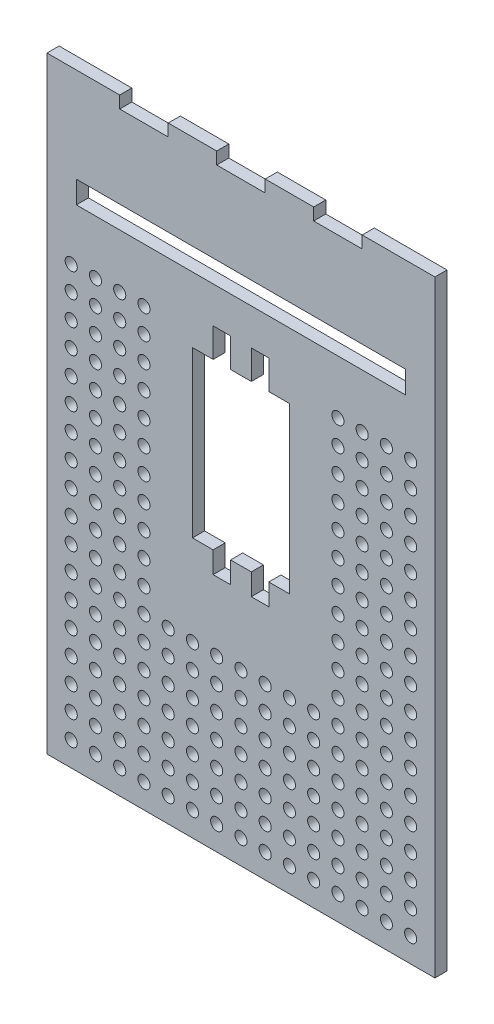
SolidWorks part; units mm, degrees
ref_plane "Front Plane" through (0, 0, 0) normal (0, 0, 1) x (1, 0, 0)
ref_plane "Top Plane" through (0, 0, 0) normal (0, 1, 0) x (1, 0, 0)
ref_plane "Right Plane" through (0, 0, 0) normal (1, 0, 0) x (0, 0, -1)
sketch "Sketch1" plane through (0, 0, 0) normal (0, 0, 1) x (1, 0, 0)
  line L1 (50.8, -79.502) -> (-50.8, -79.502)
  line L2 (50.8, -79.502) -> (50.8, 79.502)
  line L3 (50.8, 79.502) -> (-50.8, 79.502)
  line L4 (-50.8, -79.502) -> (-50.8, 79.502)
  line L5 (50.8, -79.502) -> (-50.8, 79.502) construction
  line L6 (50.8, 79.502) -> (-50.8, -79.502) construction
  point P0 (0, 0)
  dimension "D1" = 101.6
  dimension "D2" = 79.502
extrude "Boss-Extrude1" add sketch "Sketch1" along normal blind 3.175
ref_axis "Axis1" through (0, 0, 0) along (0, 0, 1)
sketch "Sketch3" plane through (0, 0, 3.175) normal (0, 0, 1) x (1, 0, 0)
  line L1 (-12.7, 31.75) -> (12.7, 31.75)
  line L2 (-12.7, 31.75) -> (-12.7, -11.43)
  line L3 (-12.7, -11.43) -> (12.7, -11.43)
  line L4 (12.7, 31.75) -> (12.7, -11.43)
  point P4 (0, 31.75)
  dimension "D1" = 25.4
  dimension "D2" = 11.43
  dimension "D3" = 31.75
extrude "Cut-Extrude1" cut sketch "Sketch3" against normal up to next
sketch "Sketch4" plane through (0, 0, 3.175) normal (0, 0, 1) x (1, 0, 0)
  line L1 (-6.35, 76.327) -> (6.35, 76.327)
  line L2 (-6.35, 76.327) -> (-6.35, 79.502)
  line L3 (-6.35, 79.502) -> (6.35, 79.502)
  line L4 (6.35, 76.327) -> (6.35, 79.502)
  line L5 (19.05, 79.502) -> (31.75, 79.502)
  line L6 (19.05, 76.327) -> (19.05, 79.502)
  line L7 (19.05, 76.327) -> (31.75, 76.327)
  line L8 (31.75, 76.327) -> (31.75, 79.502)
  line L17 (0, -1.7463) -> (0, 1.7463) construction
  line L18 (-31.75, 76.327) -> (-31.75, 79.502)
  line L19 (-19.05, 76.327) -> (-31.75, 76.327)
  line L20 (-19.05, 76.327) -> (-19.05, 79.502)
  line L21 (-19.05, 79.502) -> (-31.75, 79.502)
  line L22 (50.8, 79.502) -> (-50.8, 79.502) construction
  point P6 (0, 79.502)
  dimension "D1" = 3.175
  dimension "D2" = 12.7
  dimension "D3" = 2
  dimension "D4" = 1
extrude "Cut-Extrude2" cut sketch "Sketch4" against normal up to next
sketch "Sketch5" plane through (0, 0, 3.175) normal (0, 0, 1) x (1, 0, 0)
  line L1 (-7.286, 39.37) -> (-2.714, 39.37)
  line L2 (-7.286, 39.37) -> (-7.286, 31.75)
  line L3 (-7.286, 31.75) -> (-2.714, 31.75)
  line L4 (-2.714, 39.37) -> (-2.714, 31.75)
  line L5 (12.7, 31.75) -> (-12.7, 31.75) construction
  line L6 (0, -1.7463) -> (0, 1.7463) construction
  line L7 (2.714, 39.37) -> (2.714, 31.75)
  line L8 (7.286, 31.75) -> (2.714, 31.75)
  line L9 (7.286, 39.37) -> (7.286, 31.75)
  line L10 (7.286, 39.37) -> (2.714, 39.37)
  line L11 (-12.7, -11.43) -> (12.7, -11.43) construction
  line L12 (-7.286, -11.43) -> (-2.714, -11.43)
  line L13 (-7.286, -11.43) -> (-7.286, -17.0574)
  line L14 (-7.286, -17.0574) -> (-2.714, -17.0574)
  line L15 (-2.714, -11.43) -> (-2.714, -17.0574)
  line L16 (0, -52.7486) -> (0, 52.7486) construction
  line L17 (2.714, -11.43) -> (2.714, -17.0574)
  line L18 (7.286, -17.0574) -> (2.714, -17.0574)
  line L19 (7.286, -11.43) -> (7.286, -17.0574)
  line L20 (7.286, -11.43) -> (2.714, -11.43)
  arc A0 (-17.0133, 2.9779) -> (17.0133, 2.9779) centre (0, 0) ccw construction
  point P5 (-5, 39.37)
  dimension "D1" = 4.572
  dimension "D2" = 7.62
extrude "Cut-Extrude3" cut sketch "Sketch5" against normal up to next
sketch "Sketch6" plane through (0, 0, 3.175) normal (0, 0, 1) x (1, 0, 0)
  line L5 (-31.75, 79.502) -> (-50.8, 79.502) construction
  line L6 (-43.1171, 54.737) -> (43.1171, 54.737)
  line L7 (-43.1171, 54.737) -> (-43.1171, 48.895)
  line L8 (-43.1171, 48.895) -> (43.1171, 48.895)
  line L9 (43.1171, 54.737) -> (43.1171, 48.895)
  point P0 (0, 54.737)
  point P13 (-43.1171, 51.816)
  dimension "D1" = 5.842
  dimension "D2" = 86.2342
  dimension "D3" = 27.686
extrude "Cut-Extrude4" cut sketch "Sketch6" against normal up to next
sketch "Sketch7" plane through (0, 0, 3.175) normal (0, 0, 1) x (1, 0, 0)
  line L0 (-50.8, -1.27) -> (50.8, -1.27) construction
  line L1 (-50.8, 79.502) -> (-50.8, -79.502) construction
  line L2 (50.8, -79.502) -> (50.8, 79.502) construction
  line L3 (-31.75, 79.502) -> (-50.8, 79.502) construction
  dimension "D1" = 80.772
ref_plane "Plane1" through (0, -1.27, 0) normal (0, -1, 0) x (1, 0, 0)
sketch "Sketch8" plane through (0, 0, 3.175) normal (0, 0, 1) x (1, 0, 0)
  line L0 (-20.32, 28.2222) -> (20.32, 28.2222) construction
  line L1 (86.378, -28.9767) -> (84.2952, -28.9767)
  line L2 (86.378, -28.9767) -> (86.378, 28.2222)
  line L3 (86.378, 28.2222) -> (84.2952, 28.2222)
  line L4 (84.2952, -28.9767) -> (84.2952, 28.2222)
  line L5 (86.378, -28.9767) -> (84.2952, 28.2222) construction
  line L6 (86.378, 28.2222) -> (84.2952, -28.9767) construction
  line L7 (88.156, -6.5532) -> (88.156, 23.5712) construction
  line L8 (0, -1.7463) -> (0, 1.7463) construction
  line L9 (-86.378, 28.2222) -> (-84.2952, -28.9767) construction
  line L10 (-86.378, -28.9767) -> (-84.2952, 28.2222) construction
  line L11 (-84.2952, -28.9767) -> (-84.2952, 28.2222)
  line L12 (-86.378, 28.2222) -> (-84.2952, 28.2222)
  line L13 (-86.378, -28.9767) -> (-86.378, 28.2222)
  line L14 (-86.378, -28.9767) -> (-84.2952, -28.9767)
  point P0 (85.3366, -0.3772)
  point P8 (85.3366, 28.2222)
  point P17 (-85.3366, 28.2222)
  point P18 (-85.3366, -0.3772)
  dimension "D1" = 2.0828
  dimension "D2" = 57.1989
  dimension "D3" = 1.778
extrude "Cut-Extrude5" cut sketch "Sketch8" against normal up to next rebuild error yes
sketch "Sketch9" plane through (0, 0, 3.175) normal (0, 0, 1) x (1, 0, 0)
  line L0 (-50.8, -79.502) -> (50.8, -79.502) construction
  line L1 (-50.8, 79.502) -> (-50.8, -79.502) construction
  circle A0 centre (-44.45, -73.152) radius 1.5875
  circle A1 centre (-38.1, -73.152) radius 1.5875
  circle A2 centre (-31.75, -73.152) radius 1.5875
  circle A3 centre (-25.4, -73.152) radius 1.5875
  circle A4 centre (-19.05, -73.152) radius 1.5875
  circle A5 centre (-12.7, -73.152) radius 1.5875
  circle A6 centre (-6.35, -73.152) radius 1.5875
  circle A7 centre (0, -73.152) radius 1.5875
  circle A8 centre (6.35, -73.152) radius 1.5875
  circle A9 centre (12.7, -73.152) radius 1.5875
  circle A10 centre (19.05, -73.152) radius 1.5875
  circle A11 centre (25.4, -73.152) radius 1.5875
  circle A12 centre (31.75, -73.152) radius 1.5875
  circle A13 centre (38.1, -73.152) radius 1.5875
  circle A14 centre (44.45, -73.152) radius 1.5875
  circle A15 centre (-38.1, -66.802) radius 1.5875
  circle A16 centre (-31.75, -66.802) radius 1.5875
  circle A17 centre (-25.4, -66.802) radius 1.5875
  circle A18 centre (-19.05, -66.802) radius 1.5875
  circle A19 centre (-12.7, -66.802) radius 1.5875
  circle A20 centre (-6.35, -66.802) radius 1.5875
  circle A21 centre (0, -66.802) radius 1.5875
  circle A22 centre (6.35, -66.802) radius 1.5875
  circle A23 centre (12.7, -66.802) radius 1.5875
  circle A24 centre (19.05, -66.802) radius 1.5875
  circle A25 centre (25.4, -66.802) radius 1.5875
  circle A26 centre (31.75, -66.802) radius 1.5875
  circle A27 centre (38.1, -66.802) radius 1.5875
  circle A28 centre (44.45, -66.802) radius 1.5875
  circle A29 centre (-38.1, -60.452) radius 1.5875
  circle A30 centre (-31.75, -60.452) radius 1.5875
  circle A31 centre (-25.4, -60.452) radius 1.5875
  circle A32 centre (-19.05, -60.452) radius 1.5875
  circle A33 centre (-12.7, -60.452) radius 1.5875
  circle A34 centre (-6.35, -60.452) radius 1.5875
  circle A35 centre (0, -60.452) radius 1.5875
  circle A36 centre (6.35, -60.452) radius 1.5875
  circle A37 centre (12.7, -60.452) radius 1.5875
  circle A38 centre (19.05, -60.452) radius 1.5875
  circle A39 centre (25.4, -60.452) radius 1.5875
  circle A40 centre (31.75, -60.452) radius 1.5875
  circle A41 centre (38.1, -60.452) radius 1.5875
  circle A42 centre (44.45, -60.452) radius 1.5875
  circle A43 centre (-38.1, -54.102) radius 1.5875
  circle A44 centre (-31.75, -54.102) radius 1.5875
  circle A45 centre (-25.4, -54.102) radius 1.5875
  circle A46 centre (-19.05, -54.102) radius 1.5875
  circle A47 centre (-12.7, -54.102) radius 1.5875
  circle A48 centre (-6.35, -54.102) radius 1.5875
  circle A49 centre (0, -54.102) radius 1.5875
  circle A50 centre (6.35, -54.102) radius 1.5875
  circle A51 centre (12.7, -54.102) radius 1.5875
  circle A52 centre (19.05, -54.102) radius 1.5875
  circle A53 centre (25.4, -54.102) radius 1.5875
  circle A54 centre (31.75, -54.102) radius 1.5875
  circle A55 centre (38.1, -54.102) radius 1.5875
  circle A56 centre (44.45, -54.102) radius 1.5875
  circle A57 centre (-38.1, -47.752) radius 1.5875
  circle A58 centre (-31.75, -47.752) radius 1.5875
  circle A59 centre (-25.4, -47.752) radius 1.5875
  circle A60 centre (-19.05, -47.752) radius 1.5875
  circle A61 centre (-12.7, -47.752) radius 1.5875
  circle A62 centre (-6.35, -47.752) radius 1.5875
  circle A63 centre (0, -47.752) radius 1.5875
  circle A64 centre (6.35, -47.752) radius 1.5875
  circle A65 centre (12.7, -47.752) radius 1.5875
  circle A66 centre (19.05, -47.752) radius 1.5875
  circle A67 centre (25.4, -47.752) radius 1.5875
  circle A68 centre (31.75, -47.752) radius 1.5875
  circle A69 centre (38.1, -47.752) radius 1.5875
  circle A70 centre (44.45, -47.752) radius 1.5875
  circle A71 centre (-38.1, -41.402) radius 1.5875
  circle A72 centre (-31.75, -41.402) radius 1.5875
  circle A73 centre (-25.4, -41.402) radius 1.5875
  circle A74 centre (-19.05, -41.402) radius 1.5875
  circle A75 centre (-12.7, -41.402) radius 1.5875
  circle A76 centre (-6.35, -41.402) radius 1.5875
  circle A77 centre (0, -41.402) radius 1.5875
  circle A78 centre (6.35, -41.402) radius 1.5875
  circle A79 centre (12.7, -41.402) radius 1.5875
  circle A80 centre (19.05, -41.402) radius 1.5875
  circle A81 centre (25.4, -41.402) radius 1.5875
  circle A82 centre (31.75, -41.402) radius 1.5875
  circle A83 centre (38.1, -41.402) radius 1.5875
  circle A84 centre (44.45, -41.402) radius 1.5875
  circle A85 centre (-38.1, -35.052) radius 1.5875
  circle A86 centre (-31.75, -35.052) radius 1.5875
  circle A87 centre (-25.4, -35.052) radius 1.5875
  circle A88 centre (-19.05, -35.052) radius 1.5875
  circle A89 centre (-12.7, -35.052) radius 1.5875
  circle A90 centre (-6.35, -35.052) radius 1.5875
  circle A91 centre (0, -35.052) radius 1.5875
  circle A92 centre (6.35, -35.052) radius 1.5875
  circle A93 centre (12.7, -35.052) radius 1.5875
  circle A94 centre (19.05, -35.052) radius 1.5875
  circle A95 centre (25.4, -35.052) radius 1.5875
  circle A96 centre (31.75, -35.052) radius 1.5875
  circle A97 centre (38.1, -35.052) radius 1.5875
  circle A98 centre (44.45, -35.052) radius 1.5875
  circle A99 centre (-44.45, -66.802) radius 1.5875
  circle A100 centre (-44.45, -60.452) radius 1.5875
  circle A101 centre (-44.45, -54.102) radius 1.5875
  circle A102 centre (-44.45, -47.752) radius 1.5875
  circle A103 centre (-44.45, -41.402) radius 1.5875
  circle A104 centre (-44.45, -35.052) radius 1.5875
  circle A105 centre (-44.45, -28.702) radius 1.5875
  circle A106 centre (-38.1, -28.702) radius 1.5875
  circle A107 centre (-31.75, -28.702) radius 1.5875
  circle A108 centre (-25.4, -28.702) radius 1.5875
  circle A116 centre (25.4, -28.702) radius 1.5875
  circle A117 centre (31.75, -28.702) radius 1.5875
  circle A118 centre (38.1, -28.702) radius 1.5875
  circle A119 centre (44.45, -28.702) radius 1.5875
  circle A120 centre (-44.45, -22.352) radius 1.5875
  circle A121 centre (-38.1, -22.352) radius 1.5875
  circle A122 centre (-31.75, -22.352) radius 1.5875
  circle A123 centre (-25.4, -22.352) radius 1.5875
  circle A131 centre (25.4, -22.352) radius 1.5875
  circle A132 centre (31.75, -22.352) radius 1.5875
  circle A133 centre (38.1, -22.352) radius 1.5875
  circle A134 centre (44.45, -22.352) radius 1.5875
  circle A135 centre (-44.45, -16.002) radius 1.5875
  circle A136 centre (-38.1, -16.002) radius 1.5875
  circle A137 centre (-31.75, -16.002) radius 1.5875
  circle A138 centre (-25.4, -16.002) radius 1.5875
  circle A146 centre (25.4, -16.002) radius 1.5875
  circle A147 centre (31.75, -16.002) radius 1.5875
  circle A148 centre (38.1, -16.002) radius 1.5875
  circle A149 centre (44.45, -16.002) radius 1.5875
  circle A150 centre (-44.45, -9.652) radius 1.5875
  circle A151 centre (-38.1, -9.652) radius 1.5875
  circle A152 centre (-31.75, -9.652) radius 1.5875
  circle A153 centre (-25.4, -9.652) radius 1.5875
  circle A161 centre (25.4, -9.652) radius 1.5875
  circle A162 centre (31.75, -9.652) radius 1.5875
  circle A163 centre (38.1, -9.652) radius 1.5875
  circle A164 centre (44.45, -9.652) radius 1.5875
  circle A165 centre (-44.45, -3.302) radius 1.5875
  circle A166 centre (-38.1, -3.302) radius 1.5875
  circle A167 centre (-31.75, -3.302) radius 1.5875
  circle A168 centre (-25.4, -3.302) radius 1.5875
  circle A176 centre (25.4, -3.302) radius 1.5875
  circle A177 centre (31.75, -3.302) radius 1.5875
  circle A178 centre (38.1, -3.302) radius 1.5875
  circle A179 centre (44.45, -3.302) radius 1.5875
  circle A180 centre (-44.45, 3.048) radius 1.5875
  circle A181 centre (-38.1, 3.048) radius 1.5875
  circle A182 centre (-31.75, 3.048) radius 1.5875
  circle A183 centre (-25.4, 3.048) radius 1.5875
  circle A191 centre (25.4, 3.048) radius 1.5875
  circle A192 centre (31.75, 3.048) radius 1.5875
  circle A193 centre (38.1, 3.048) radius 1.5875
  circle A194 centre (44.45, 3.048) radius 1.5875
  circle A195 centre (-44.45, 9.398) radius 1.5875
  circle A196 centre (-38.1, 9.398) radius 1.5875
  circle A197 centre (-31.75, 9.398) radius 1.5875
  circle A198 centre (-25.4, 9.398) radius 1.5875
  circle A206 centre (25.4, 9.398) radius 1.5875
  circle A207 centre (31.75, 9.398) radius 1.5875
  circle A208 centre (38.1, 9.398) radius 1.5875
  circle A209 centre (44.45, 9.398) radius 1.5875
  circle A210 centre (-44.45, 15.748) radius 1.5875
  circle A211 centre (-38.1, 15.748) radius 1.5875
  circle A212 centre (-31.75, 15.748) radius 1.5875
  circle A213 centre (-25.4, 15.748) radius 1.5875
  circle A221 centre (25.4, 15.748) radius 1.5875
  circle A222 centre (31.75, 15.748) radius 1.5875
  circle A223 centre (38.1, 15.748) radius 1.5875
  circle A224 centre (44.45, 15.748) radius 1.5875
  circle A225 centre (-44.45, 22.098) radius 1.5875
  circle A226 centre (-38.1, 22.098) radius 1.5875
  circle A227 centre (-31.75, 22.098) radius 1.5875
  circle A228 centre (-25.4, 22.098) radius 1.5875
  circle A236 centre (25.4, 22.098) radius 1.5875
  circle A237 centre (31.75, 22.098) radius 1.5875
  circle A238 centre (38.1, 22.098) radius 1.5875
  circle A239 centre (44.45, 22.098) radius 1.5875
  circle A240 centre (-44.45, 28.448) radius 1.5875
  circle A241 centre (-38.1, 28.448) radius 1.5875
  circle A242 centre (-31.75, 28.448) radius 1.5875
  circle A243 centre (-25.4, 28.448) radius 1.5875
  circle A251 centre (25.4, 28.448) radius 1.5875
  circle A252 centre (31.75, 28.448) radius 1.5875
  circle A253 centre (38.1, 28.448) radius 1.5875
  circle A254 centre (44.45, 28.448) radius 1.5875
  circle A255 centre (-44.45, 34.798) radius 1.5875
  circle A256 centre (-38.1, 34.798) radius 1.5875
  circle A257 centre (-31.75, 34.798) radius 1.5875
  circle A258 centre (-25.4, 34.798) radius 1.5875
  circle A266 centre (25.4, 34.798) radius 1.5875
  circle A267 centre (31.75, 34.798) radius 1.5875
  circle A268 centre (38.1, 34.798) radius 1.5875
  circle A269 centre (44.45, 34.798) radius 1.5875
  circle A285 centre (-19.05, -28.702) radius 1.5875 [skipped]
  circle A286 centre (-12.7, -28.702) radius 1.5875 [skipped]
  circle A287 centre (-6.35, -28.702) radius 1.5875 [skipped]
  circle A288 centre (0, -28.702) radius 1.5875 [skipped]
  circle A289 centre (6.35, -28.702) radius 1.5875 [skipped]
  circle A290 centre (12.7, -28.702) radius 1.5875 [skipped]
  circle A291 centre (19.05, -28.702) radius 1.5875 [skipped]
  circle A292 centre (-19.05, -22.352) radius 1.5875 [skipped]
  circle A293 centre (-12.7, -22.352) radius 1.5875 [skipped]
  circle A294 centre (-6.35, -22.352) radius 1.5875 [skipped]
  circle A295 centre (0, -22.352) radius 1.5875 [skipped]
  circle A296 centre (6.35, -22.352) radius 1.5875 [skipped]
  circle A297 centre (12.7, -22.352) radius 1.5875 [skipped]
  circle A298 centre (19.05, -22.352) radius 1.5875 [skipped]
  circle A299 centre (-19.05, -16.002) radius 1.5875 [skipped]
  circle A300 centre (-12.7, -16.002) radius 1.5875 [skipped]
  circle A301 centre (-6.35, -16.002) radius 1.5875 [skipped]
  circle A302 centre (0, -16.002) radius 1.5875 [skipped]
  circle A303 centre (6.35, -16.002) radius 1.5875 [skipped]
  circle A304 centre (12.7, -16.002) radius 1.5875 [skipped]
  circle A305 centre (19.05, -16.002) radius 1.5875 [skipped]
  circle A306 centre (-19.05, -9.652) radius 1.5875 [skipped]
  circle A307 centre (-12.7, -9.652) radius 1.5875 [skipped]
  circle A308 centre (-6.35, -9.652) radius 1.5875 [skipped]
  circle A309 centre (0, -9.652) radius 1.5875 [skipped]
  circle A310 centre (6.35, -9.652) radius 1.5875 [skipped]
  circle A311 centre (12.7, -9.652) radius 1.5875 [skipped]
  circle A312 centre (19.05, -9.652) radius 1.5875 [skipped]
  circle A313 centre (-19.05, -3.302) radius 1.5875 [skipped]
  circle A314 centre (-12.7, -3.302) radius 1.5875 [skipped]
  circle A315 centre (-6.35, -3.302) radius 1.5875 [skipped]
  circle A316 centre (0, -3.302) radius 1.5875 [skipped]
  circle A317 centre (6.35, -3.302) radius 1.5875 [skipped]
  circle A318 centre (12.7, -3.302) radius 1.5875 [skipped]
  circle A319 centre (19.05, -3.302) radius 1.5875 [skipped]
  circle A320 centre (-19.05, 3.048) radius 1.5875 [skipped]
  circle A321 centre (-12.7, 3.048) radius 1.5875 [skipped]
  circle A322 centre (-6.35, 3.048) radius 1.5875 [skipped]
  circle A323 centre (0, 3.048) radius 1.5875 [skipped]
  circle A324 centre (6.35, 3.048) radius 1.5875 [skipped]
  circle A325 centre (12.7, 3.048) radius 1.5875 [skipped]
  circle A326 centre (19.05, 3.048) radius 1.5875 [skipped]
  circle A327 centre (-19.05, 9.398) radius 1.5875 [skipped]
  circle A328 centre (-12.7, 9.398) radius 1.5875 [skipped]
  circle A329 centre (-6.35, 9.398) radius 1.5875 [skipped]
  circle A330 centre (0, 9.398) radius 1.5875 [skipped]
  circle A331 centre (6.35, 9.398) radius 1.5875 [skipped]
  circle A332 centre (12.7, 9.398) radius 1.5875 [skipped]
  circle A333 centre (19.05, 9.398) radius 1.5875 [skipped]
  circle A334 centre (-19.05, 15.748) radius 1.5875 [skipped]
  circle A335 centre (-12.7, 15.748) radius 1.5875 [skipped]
  circle A336 centre (-6.35, 15.748) radius 1.5875 [skipped]
  circle A337 centre (0, 15.748) radius 1.5875 [skipped]
  circle A338 centre (6.35, 15.748) radius 1.5875 [skipped]
  circle A339 centre (12.7, 15.748) radius 1.5875 [skipped]
  circle A340 centre (19.05, 15.748) radius 1.5875 [skipped]
  circle A341 centre (-19.05, 22.098) radius 1.5875 [skipped]
  circle A342 centre (-12.7, 22.098) radius 1.5875 [skipped]
  circle A343 centre (-6.35, 22.098) radius 1.5875 [skipped]
  circle A344 centre (0, 22.098) radius 1.5875 [skipped]
  circle A345 centre (6.35, 22.098) radius 1.5875 [skipped]
  circle A346 centre (12.7, 22.098) radius 1.5875 [skipped]
  circle A347 centre (19.05, 22.098) radius 1.5875 [skipped]
  circle A348 centre (-19.05, 28.448) radius 1.5875 [skipped]
  circle A349 centre (-12.7, 28.448) radius 1.5875 [skipped]
  circle A350 centre (-6.35, 28.448) radius 1.5875 [skipped]
  circle A351 centre (0, 28.448) radius 1.5875 [skipped]
  circle A352 centre (6.35, 28.448) radius 1.5875 [skipped]
  circle A353 centre (12.7, 28.448) radius 1.5875 [skipped]
  circle A354 centre (19.05, 28.448) radius 1.5875 [skipped]
  circle A355 centre (-19.05, 34.798) radius 1.5875 [skipped]
  circle A356 centre (-12.7, 34.798) radius 1.5875 [skipped]
  circle A357 centre (-6.35, 34.798) radius 1.5875 [skipped]
  circle A358 centre (0, 34.798) radius 1.5875 [skipped]
  circle A359 centre (6.35, 34.798) radius 1.5875 [skipped]
  circle A360 centre (12.7, 34.798) radius 1.5875 [skipped]
  circle A361 centre (19.05, 34.798) radius 1.5875 [skipped]
  circle A362 centre (-19.05, 41.148) radius 1.5875 [skipped]
  circle A363 centre (-12.7, 41.148) radius 1.5875 [skipped]
  circle A364 centre (-6.35, 41.148) radius 1.5875 [skipped]
  circle A365 centre (0, 41.148) radius 1.5875 [skipped]
  circle A366 centre (6.35, 41.148) radius 1.5875 [skipped]
  circle A367 centre (12.7, 41.148) radius 1.5875 [skipped]
  circle A368 centre (19.05, 41.148) radius 1.5875 [skipped]
  circle A369 centre (-44.45, 41.148) radius 1.5875 [skipped]
  circle A370 centre (-38.1, 41.148) radius 1.5875 [skipped]
  circle A371 centre (-31.75, 41.148) radius 1.5875 [skipped]
  circle A372 centre (-25.4, 41.148) radius 1.5875 [skipped]
  circle A373 centre (25.4, 41.148) radius 1.5875 [skipped]
  circle A374 centre (31.75, 41.148) radius 1.5875 [skipped]
  circle A375 centre (38.1, 41.148) radius 1.5875 [skipped]
  circle A376 centre (44.45, 41.148) radius 1.5875 [skipped]
  dimension "D1" = 3.175
  dimension "D2" = 6.35
  dimension "D3" = 6.35
  dimension "D4" = 15
  dimension "D5" = 19
extrude "Cut-Extrude6" cut sketch "Sketch9" against normal up to next (3.175 mm away)
